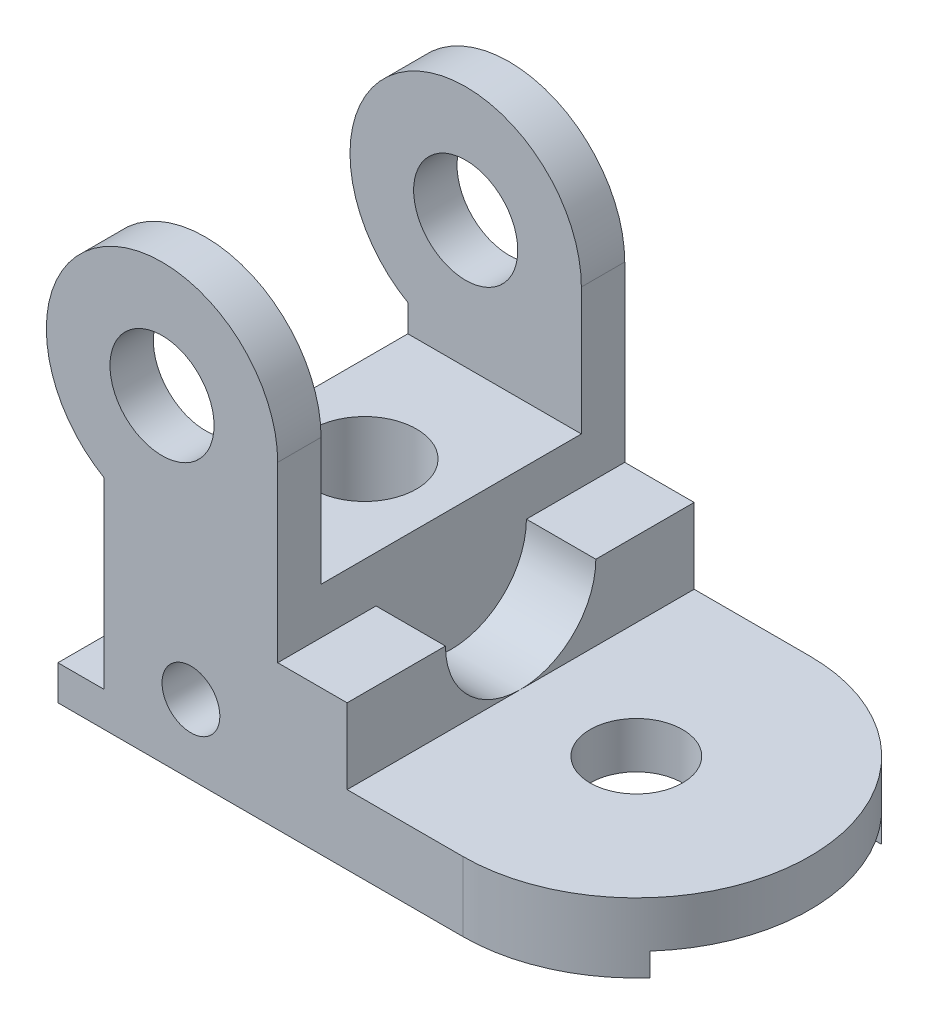
SolidWorks part; units mm, degrees
material "1023 Chapa de aço carbono (SS)"
ref_plane "Plano frontal" through (0, 0, 0) normal (0, 0, 1) x (1, 0, 0)
ref_plane "Plano superior" through (0, 0, 0) normal (0, 1, 0) x (1, 0, 0)
ref_plane "Plano direito" through (0, 0, 0) normal (1, 0, 0) x (0, 0, -1)
sketch "Esboço1" plane through (0, 0, 0) normal (0, 1, 0) x (1, 0, 0)
  line L0 (0, 30) -> (-70, 30)
  line L1 (-70, 30) -> (-70, -30)
  line L2 (-70, -30) -> (0, -30)
  arc A0 (0, -30) -> (0, 30) centre (0, 0) ccw
  dimension "D1" = 60
  dimension "D2" = 100
extrude "Ressalto-extrusão1" add sketch "Esboço1" along normal blind 33
sketch "Esboço2" plane through (0, 0, 0) normal (0, 1, 0) x (1, 0, 0)
  circle A0 centre (0, 0) radius 8
  dimension "D1" = 16
extrude "Corte-extrusão6" cut sketch "Esboço2" against normal through all and the other way through all contours A0
sketch "Esboço5" plane through (0, 33, 0) normal (0, 1, 0) x (1, 0, 0)
  line L0 (-20, 30) -> (-20, -30)
  line L1 (-32, 30) -> (-32, -30)
  line L3 (0, 30) -> (-70, 30)
  line L4 (-70, 30) -> (-70, -30)
  line L5 (-70, -30) -> (0, -30)
  line L6 (0, 30) -> (-70, 30)
  line L7 (-70, 30) -> (-70, -30)
  line L8 (-70, -30) -> (0, -30)
  arc A1 (0, -30) -> (0, 30) centre (0, 0) ccw
  arc A2 (0, -30) -> (0, 30) centre (0, 0) ccw
  dimension "D2" = 12
  dimension "D3" = 20
  dimension "D1" = 0
extrude "Corte-extrusão10" cut sketch "Esboço5" against normal blind 21 contours L5 L0 L4 L3 region at (2.2956, 33, 0)
extrude "Corte-extrusão11" cut sketch "Esboço5<5>" against normal blind 8 contours L5 L1 L0 region at (-26, 33, 0)
sketch "Esboço5<5>" plane through (0, 33, 0) normal (0, 1, 0) x (1, 0, 0) same geometry as "Esboço5"
sketch "Esboço7" plane through (-20, 0, 0) normal (1, 0, 0) x (0, 0, -1)
  line L0 (30, 25) -> (-30, 25) construction
  line L1 (30, 12) -> (-30, 12) construction
  circle A0 centre (0, 25) radius 13
extrude "Corte-extrusão12" cut sketch "Esboço7" against normal up to surface (12 mm away) up to face at (-32, 29, 0)
sketch "Esboço8" plane through (0, 0, 30) normal (0, 0, 1) x (1, 0, 0)
  line L0 (-70, 0) -> (0, 0) construction
  line L1 (-32, 33) -> (-32, 55)
  line L2 (-62, 33) -> (-62, 37.6795)
  line L4 (-70, 33) -> (-32, 33) construction
  line L5 (-32, 33) -> (-62, 33)
  arc A0 (-32, 55) -> (-62, 37.6795) centre (-52, 55) ccw
  circle A2 centre (-52, 55) radius 9
  dimension "D1" = 18
  dimension "D2" = 40
  dimension "D3" = 55
  dimension "D4" = 30
extrude "Ressalto-extrusão2" add sketch "Esboço8" against normal up to surface (60 mm away) up to face at (-30.5, 17.5, -30)
extrude "Corte-extrusão13" cut sketch "Esboço8<2>" against normal blind 45 from offset 7.5 offset against normal yes
sketch "Esboço8<2>" plane through (0, 0, 30) normal (0, 0, 1) x (1, 0, 0) same geometry as "Esboço8"
sketch "Esboço9" plane through (0, 0, 30) normal (0, 0, 1) x (1, 0, 0)
  line L0 (-70, 33) -> (-70, 0) construction
  line L1 (-62, 33) -> (-70, 33)
  line L2 (-62, 33) -> (-62, 6)
  line L3 (-62, 6) -> (-70, 6)
  line L4 (-70, 33) -> (-70, 6)
  line L5 (-70, 0) -> (0, 0) construction
  dimension "D1" = 6
extrude "Corte-extrusão14" cut sketch "Esboço9" against normal through all contours L2 L1 L4 L3
sketch "Esboço10" plane through (0, 33, 0) normal (0, 1, 0) x (1, 0, 0)
  line L0 (-62, 22.5) -> (-32, -22.5) construction
  circle A0 centre (-47, 0) radius 9
  dimension "D1" = 18
extrude "Corte-extrusão15" cut sketch "Esboço10" against normal through all contours A0
sketch "Esboço11" plane through (0, 0, 0) normal (0, 0, 1) x (1, 0, 0)
  line L0 (-32, 25) -> (-32, 55) construction
  line L2 (-70, 0) -> (0, 0) construction
  circle A0 centre (-47, 12) radius 5
  dimension "D1" = 10
  dimension "D2" = 15
  dimension "D3" = 12
extrude "Corte-extrusão18" cut sketch "Esboço11" against normal through all both and the other way through all
sketch "Esboço12" plane through (-70, 0, 0) normal (-1, 0, 0) x (0, 0, 1)
  line L0 (-30, 0) -> (30, 0) construction
  line L1 (-20, 0) -> (20, 0)
  line L2 (-20, 0) -> (-20, 4)
  line L3 (-20, 4) -> (20, 4)
  line L4 (20, 0) -> (20, 4)
  line L5 (0, 0) -> (0, 4)
  point P9 (20, 2)
  line M8 (-30, 0) -> (30, 0)
  dimension "D1" = 4
  dimension "D2" = 40
extrude "Corte-extrusão19" cut sketch "Esboço12" against normal through all contours L5 L3 L2 M8 | L5 L1 L4 L3 region at (-70, 2, -10) region at (-70, 2, 10)
